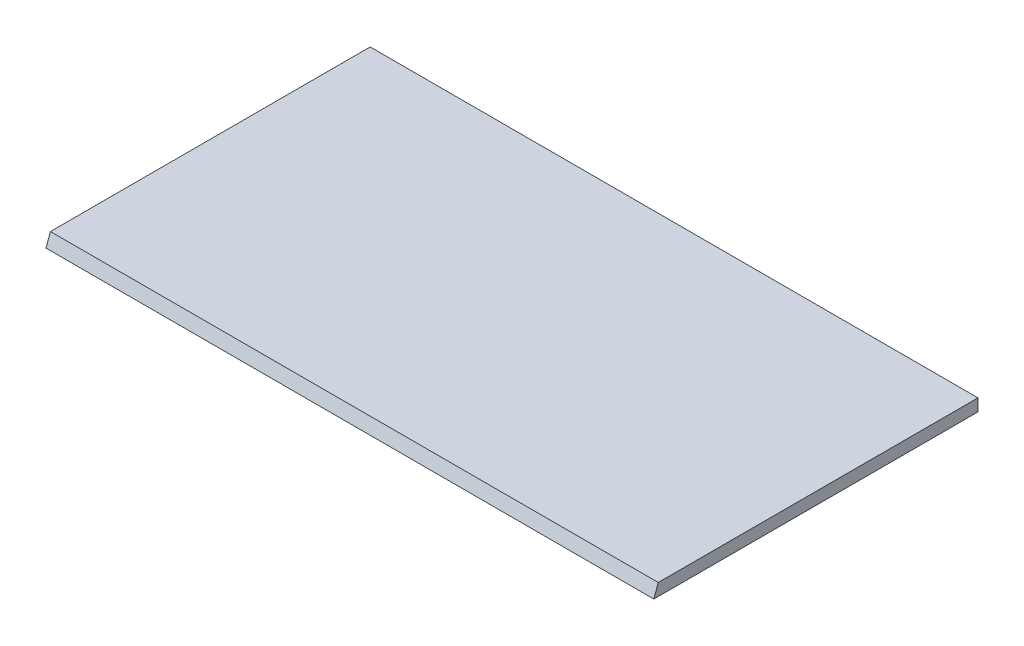
SolidWorks part; units mm, degrees
ref_plane "Plan de face" through (0, 0, 0) normal (0, 0, 1) x (1, 0, 0)
ref_plane "Plan de dessus" through (0, 0, 0) normal (0, 1, 0) x (1, 0, 0)
ref_plane "Plan de droite" through (0, 0, 0) normal (1, 0, 0) x (0, 0, -1)
sketch "Esquisse1" plane through (0, 0, 0) normal (0, 1, 0) x (1, 0, 0)
  line L1 (0, 0) -> (150, 0)
  line L2 (0, 0) -> (0, 80)
  line L3 (0, 80) -> (150, 80)
  line L4 (150, 0) -> (150, 80)
  dimension "D1" = 150
  dimension "D2" = 80
extrude "Boss.-Extru.1" add sketch "Esquisse1" along normal blind 3
chamfer "Chanfrein2" distance 3 angle 20 1 edges at (75, 3, 0) first distance on face at (75, 1.5, 0)
